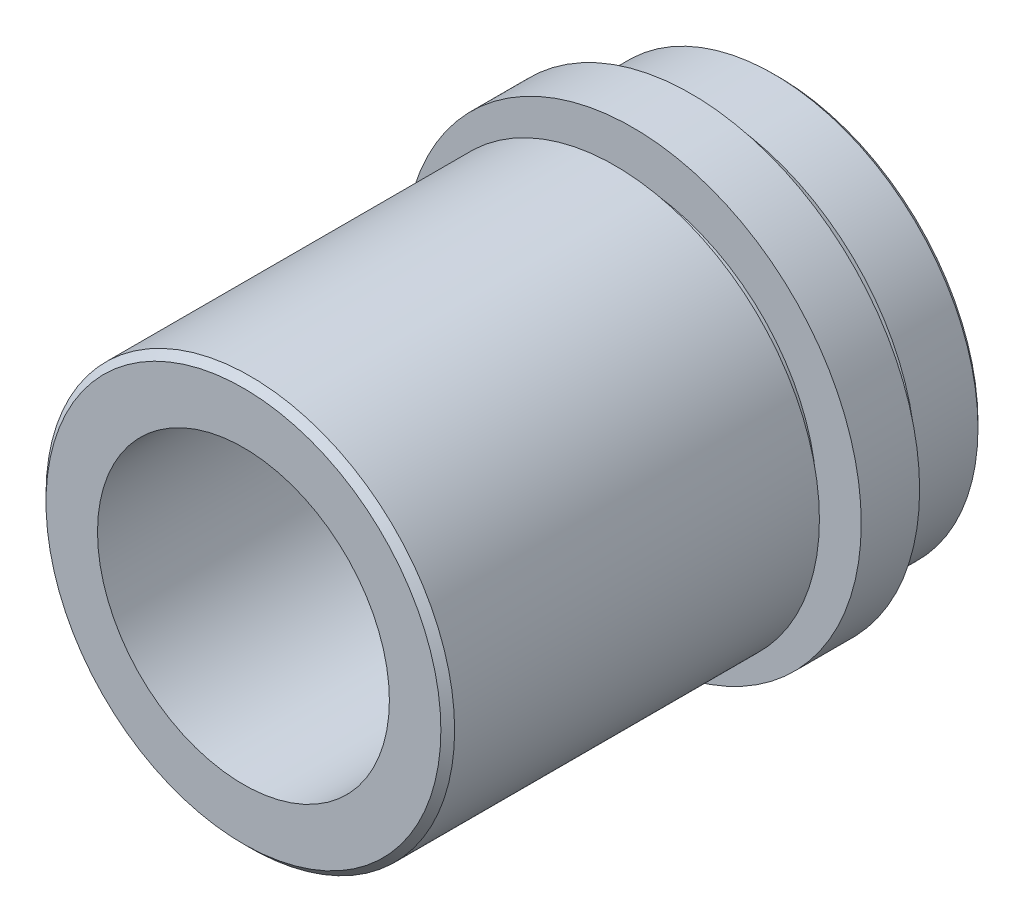
SolidWorks part; units mm, degrees
ref_plane "Płaszczyzna przednia" through (0, 0, 0) normal (0, 0, 1) x (1, 0, 0)
ref_plane "Płaszczyzna górna" through (0, 0, 0) normal (0, 1, 0) x (1, 0, 0)
ref_plane "Płaszczyzna prawa" through (0, 0, 0) normal (1, 0, 0) x (0, 0, -1)
sketch "Szkic1" plane through (0, 0, 0) normal (1, 0, 0) x (0, 0, -1)
  line L0 (-15, 0) -> (-15, 23.5)
  line L1 (-15, 23.5) -> (-9, 23.5)
  line L2 (-9, 23.5) -> (-9, 0)
  line L3 (-9, 0) -> (-15, 0)
  line L4 (-9, 0) -> (-15, 0) construction
sketch "Szkic2" plane through (0, 0, 0) normal (1, 0, 0) x (0, 0, -1)
  line L0 (-55, 0) -> (-55, 21)
  line L1 (-55, 21) -> (-15, 21)
  line L2 (-15, 21) -> (-15, 0)
  line L3 (-15, 0) -> (-55, 0)
  line L4 (-15, 0) -> (-55, 0) construction
sketch "Szkic3" plane through (0, 0, 0) normal (1, 0, 0) x (0, 0, -1)
  line L0 (-55, 20.2929) -> (-54.2929, 21)
  line L1 (-54.2929, 21) -> (-55, 21)
  line L2 (-55, 21) -> (-55, 20.2929)
  line L3 (-15, 0) -> (-55, 0) construction
sketch "Szkic4" plane through (0, 0, 0) normal (1, 0, 0) x (0, 0, -1)
  line L0 (-16.8, 21) -> (-16.8, 18.9)
  line L1 (-16.8, 18.9) -> (-15, 18.9)
  line L2 (-15, 18.9) -> (-15, 21)
  line L3 (-15, 21) -> (-16.8, 21)
  line L4 (-15, 0) -> (-55, 0) construction
ref_plane "Płaszczyzna1" through (0, 0, 9) normal (0, 0, 1) x (1, 0, 0)
ref_plane "Płaszczyzna2" through (0, 0, 55) normal (0, 0, 1) x (1, 0, 0)
sketch "Szkic5" plane through (0, 0, 0) normal (1, 0, 0) x (0, 0, -1)
  line L0 (-9, 0) -> (-9, 21)
  line L1 (-9, 21) -> (0, 21)
  line L2 (0, 21) -> (0, 0)
  line L3 (0, 0) -> (-9, 0)
  line L4 (0, 0) -> (-9, 0) construction
sketch "Szkic6" plane through (0, 0, 0) normal (1, 0, 0) x (0, 0, -1)
  line L0 (-55, 0) -> (-55, 15)
  line L1 (-55, 15) -> (-1, 15)
  line L2 (-1, 15) -> (0, 16)
  line L3 (0, 16) -> (0, 0)
  line L4 (0, 0) -> (-55, 0)
  line L5 (0, 0) -> (-55, 0) construction
sketch "Szkic7" plane through (0, 0, 0) normal (1, 0, 0) x (0, 0, -1)
  line L0 (-0.5, 21) -> (0, 20.5)
  line L1 (0, 20.5) -> (0, 21)
  line L2 (0, 21) -> (-0.5, 21)
  line L3 (0, 0) -> (-9, 0) construction
sketch "Szkic8" plane through (0, 0, 0) normal (1, 0, 0) x (0, 0, -1)
  line L0 (-9, 18.9) -> (-6.9, 18.9)
  line L1 (-6.9, 18.9) -> (-6.9, 21)
  line L2 (-6.9, 21) -> (-9, 21)
  line L3 (-9, 21) -> (-9, 18.9)
  line L4 (0, 0) -> (-9, 0) construction
revolve "Obrót1" add sketch "Szkic1" angle 360 about L4 reverse direction yes
revolve "Obrót2" add sketch "Szkic2" angle 360 about L4 reverse direction yes
revolve "Wycięcie-obrót1" cut sketch "Szkic3" angle 360 about L3 reverse direction yes
revolve "Wycięcie-obrót2" cut sketch "Szkic4" angle 360 about L4 reverse direction yes
revolve "Obrót3" add sketch "Szkic5" angle 360 about L4 reverse direction yes
revolve "Wycięcie-obrót3" cut sketch "Szkic6" angle 360 about L5 reverse direction yes
revolve "Wycięcie-obrót4" cut sketch "Szkic7" angle 360 about L3 reverse direction yes
revolve "Wycięcie-obrót5" cut sketch "Szkic8" angle 360 about L4 reverse direction yes
ref_plane "IP1 XY" through (0, 0, 9) normal (0, 0, 1) x (1, 0, 0)
ref_plane "IP1 XZ" through (0, 0, 0) normal (0, -1, 0) x (-1, 0, 0)
ref_plane "IP1 YZ" through (0, 0, 0) normal (1, 0, 0) x (0, 0, -1)
ref_axis "IP1 X" through (-80.9, 0, 9) along (1, 0, 0)
ref_axis "IP1 Y" through (0, -50, 9) along (0, 1, 0)
ref_axis "IP1 Z" through (0, 0, 80.9) along (0, 0, -1)
sketch3d "IP1"
  point P0 (0, 0, 9)
ref_plane "IP2 XY" through (0, 0, 55) normal (0, 0, 1) x (1, 0, 0)
ref_plane "IP2 XZ" through (0, 0, 0) normal (0, -1, 0) x (-1, 0, 0)
ref_plane "IP2 YZ" through (0, 0, 0) normal (1, 0, 0) x (0, 0, -1)
ref_axis "IP2 X" through (-80.9, 0, 55) along (1, 0, 0)
ref_axis "IP2 Y" through (0, -50, 55) along (0, 1, 0)
ref_axis "IP2 Z" through (0, 0, 80.9) along (0, 0, -1)
sketch3d "IP2"
  point P0 (0, 0, 55)
ref_plane "IP3 XY" through (0, 0, 0) normal (0, 0, 1) x (1, 0, 0)
ref_plane "IP3 XZ" through (0, 0, 0) normal (0, -1, 0) x (-1, 0, 0)
ref_plane "IP3 YZ" through (0, 0, 0) normal (1, 0, 0) x (0, 0, -1)
ref_axis "IP3 X" through (-80.9, 0, 0) along (1, 0, 0)
ref_axis "IP3 Y" through (0, -50, 0) along (0, 1, 0)
ref_axis "IP3 Z" through (0, 0, 80.9) along (0, 0, -1)
sketch3d "IP3"
  point P0 (0, 0, 0)
